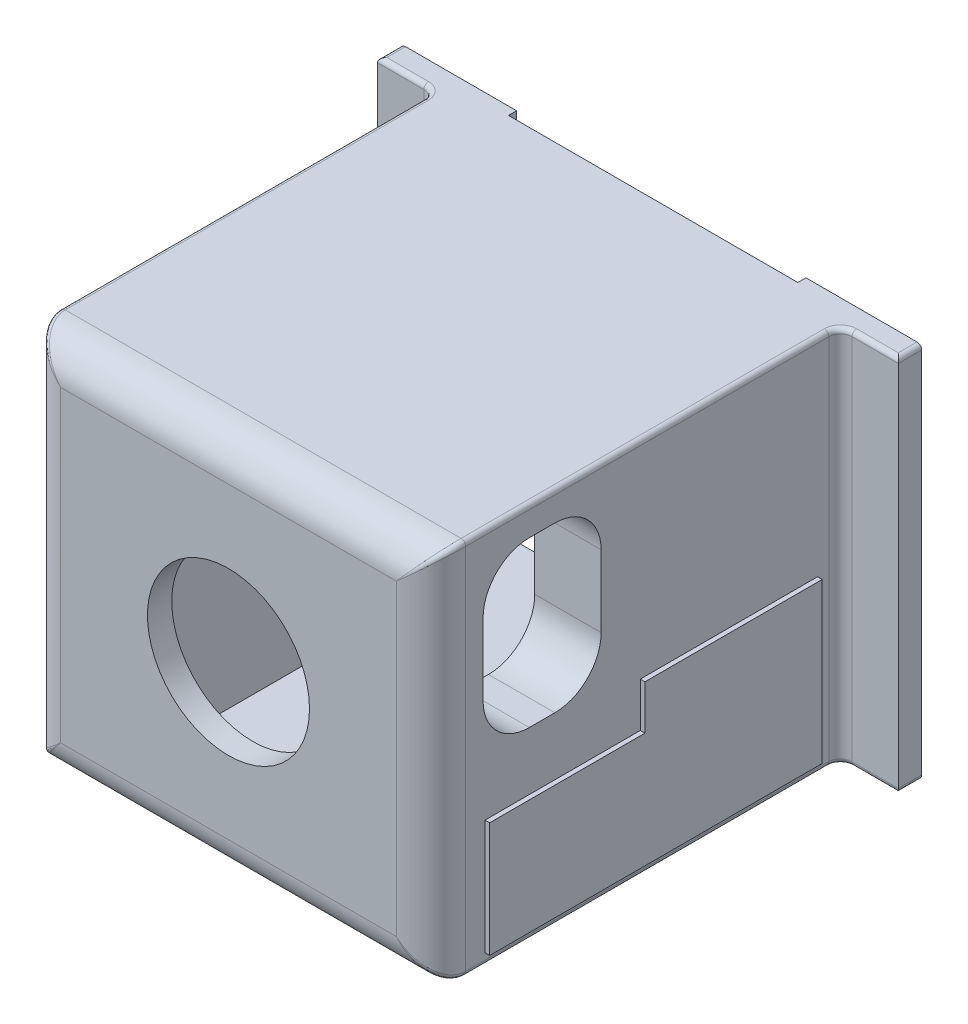
SolidWorks part; units mm, degrees
ref_plane "Front Plane" through (0, 0, 0) normal (0, 0, 1) x (1, 0, 0)
ref_plane "Top Plane" through (0, 0, 0) normal (0, 1, 0) x (1, 0, 0)
ref_plane "Right Plane" through (0, 0, 0) normal (1, 0, 0) x (0, 0, -1)
sketch "Sketch1" plane through (0, 0, 0) normal (0, 1, 0) x (1, 0, 0)
  line L0 (0, -122.8917) -> (0, 166.9975) construction
  line L1 (-87.5, -71.8994) -> (87.5, -71.8994)
  line L2 (87.5, -71.8994) -> (87.5, 105.0006)
  line L3 (87.5, 105.0006) -> (112.5, 105.0006)
  line L4 (112.5, 105.0006) -> (112.5, 115.1006)
  line L5 (112.5, 115.1006) -> (62.5, 115.1006)
  line L6 (62.5, 115.1006) -> (62.5, 111.6006)
  line L7 (62.5, 111.6006) -> (-62.5, 111.6006)
  line L8 (-62.5, 115.1006) -> (-62.5, 111.6006)
  line L9 (-112.5, 115.1006) -> (-62.5, 115.1006)
  line L10 (-112.5, 105.0006) -> (-112.5, 115.1006)
  line L11 (-87.5, 105.0006) -> (-112.5, 105.0006)
  line L12 (-87.5, -71.8994) -> (-87.5, 105.0006)
  point P12 (0, -71.8994)
  point P14 (0, 111.6006)
  dimension "D1" = 87.5
  dimension "D2" = 176.9
  dimension "D3" = 25
  dimension "D4" = 10.1
  dimension "D5" = 50
  dimension "D6" = 3.5
extrude "Boss-Extrude1" add sketch "Sketch1" along normal blind 163
sketch "Sketch2" plane through (87.5, 0, 0) normal (1, 0, 0) x (0, 0, -1)
  line L0 (-23.8994, 163) -> (-23.8994, 0) construction
  line L1 (-71.8994, 163) -> (105.0006, 163) construction
  line L2 (-71.8994, 0) -> (105.0006, 0) construction
  line L3 (-71.8994, 115) -> (115.1006, 115) construction
  line L4 (-71.8994, 163) -> (-71.8994, 0) construction
  line L5 (115.1006, 163) -> (115.1006, 0) construction
  line L7 (-18.3994, 79.5) -> (-29.3994, 79.5)
  line L8 (1.6006, 99.5) -> (1.6006, 130.5)
  line L9 (-18.3994, 150.5) -> (-29.3994, 150.5)
  line L10 (-49.3994, 99.5) -> (-49.3994, 130.5)
  line L11 (1.6006, 79.5) -> (-49.3994, 150.5) construction
  line L12 (1.6006, 150.5) -> (-49.3994, 79.5) construction
  arc A0 (-18.3994, 79.5) -> (1.6006, 99.5) centre (-18.3994, 99.5) ccw
  arc A1 (-29.3994, 79.5) -> (-49.3994, 99.5) centre (-29.3994, 99.5) cw
  arc A2 (1.6006, 130.5) -> (-18.3994, 150.5) centre (-18.3994, 130.5) ccw
  arc A3 (-29.3994, 150.5) -> (-49.3994, 130.5) centre (-29.3994, 130.5) ccw
  point P12 (-23.8994, 115)
  dimension "D5" = 20
  dimension "D1" = 48
  dimension "D2" = 48
  dimension "D3" = 71
  dimension "D4" = 51
sketch "Sketch3" plane through (0, 0, -111.6006) normal (0, 0, -1) x (-1, 0, 0)
  line L0 (0, 163) -> (0, 0) construction
  line L1 (-62.5, 163) -> (62.5, 163) construction
  line L2 (-62.5, 81.5) -> (62.5, 81.5) construction
  line L3 (-62.5, 163) -> (-62.5, 0) construction
  line L4 (62.5, 163) -> (62.5, 0) construction
  line L6 (58.8268, 5.2149) -> (-58.8268, 5.2149)
  line L7 (58.8268, 5.2149) -> (58.8268, 157.7851)
  line L8 (58.8268, 157.7851) -> (-58.8268, 157.7851)
  line L9 (-58.8268, 5.2149) -> (-58.8268, 157.7851)
  line L10 (58.8268, 5.2149) -> (-58.8268, 157.7851) construction
  line L11 (58.8268, 157.7851) -> (-58.8268, 5.2149) construction
  point P11 (0, 81.5)
extrude "Cut-Extrude2" cut sketch "Sketch3" against normal blind 173
extrude "Cut-Extrude3" cut sketch "Sketch2" against normal blind 113
sketch "Sketch4" plane through (0, 0, 71.8994) normal (0, 0, 1) x (1, 0, 0)
  line L0 (0, 163) -> (0, 0) construction
  line L1 (-87.5, 163) -> (87.5, 163) construction
  line L2 (-112.5, 81.5) -> (112.5, 81.5) construction
  line L3 (-112.5, 163) -> (-112.5, 0) construction
  line L4 (112.5, 163) -> (112.5, 0) construction
  circle A0 centre (0, 81.5) radius 35
  dimension "D1" = 70
extrude "Cut-Extrude4" cut sketch "Sketch4" against normal blind 113
ref_plane "Plane1" through (89.5, 0, 0) normal (1, 0, 0) x (0, 0, -1)
sketch "Sketch6" plane through (89.5, 0, 0) normal (1, 0, 0) x (0, 0, -1)
  line L0 (-71.8994, 81.5) -> (105.0006, 81.5) construction
  line L1 (-71.8994, 163) -> (-71.8994, 0) construction
  line L2 (105.0006, 163) -> (105.0006, 0) construction
  line L3 (16.5506, 163) -> (16.5506, 75.6291) construction
  line L4 (-71.8994, 163) -> (105.0006, 163) construction
  line L5 (-71.8994, 0) -> (105.0006, 0) construction
  line L7 (-50.5332, 6.7436) -> (93.1087, 6.7436)
  line L8 (93.1087, 6.7436) -> (93.1087, 75.6291)
  line L9 (93.1087, 75.6291) -> (16.5506, 75.6291)
  line L12 (16.5506, 48.6228) -> (16.5506, 0) construction
  line L13 (16.5506, 75.6291) -> (16.5506, 56.4101)
  line L14 (16.5506, 56.4101) -> (-50.5332, 56.4101)
  line L15 (-50.5332, 56.4101) -> (-50.5332, 6.7436)
extrude "Boss-Extrude2" add sketch "Sketch6" along normal blind 2 separate body
sketch "Sketch7" plane through (91.5, 0, 0) normal (1, 0, 0) x (0, 0, -1)
  circle A0 centre (-41.8079, 11.8377) radius 2.5
  circle A1 centre (-41.8079, 51.4736) radius 2.5
  circle A2 centre (83.571, 11.8377) radius 2.5
  circle A3 centre (83.571, 70.0782) radius 2.5
  point P8 (0, 0)
  dimension "D1" = 5
extrude "Boss-Extrude3" add sketch "Sketch7" against normal blind 10
fillet "Fillet1" radius 5 2 edges at (-87.5, 81.5, -105.0006) (87.5, 81.5, -105.0006)
fillet "Fillet2" radius 15 4 edges at (0, 0, 71.8994) (-87.5, 81.5, 71.8994) (0, 163, 71.8994) (87.5, 81.5, 71.8994)
fillet "Fillet4" radius 2 20 edges at (83.1066, 158.6066, 67.506) (87.5, 163, -21.5506) (88.9645, 163, -103.5361) (83.1066, 4.3934, 67.506) (87.5, 0, -21.5506) (88.9645, 0, -103.5361) (-83.1066, 158.6066, 67.506) (-87.5, 163, -21.5506) (-88.9645, 163, -103.5361) (-83.1066, 4.3934, 67.506) (-87.5, 0, -21.5506) (-88.9645, 0, -103.5361) (112.5, 163, -110.0506) (102.5, 163, -105.0006) (102.5, 0, -105.0006) (112.5, 0, -110.0506) (-112.5, 163, -110.0506) (-102.5, 163, -105.0006) (-102.5, 0, -105.0006) (-112.5, 0, -110.0506)
